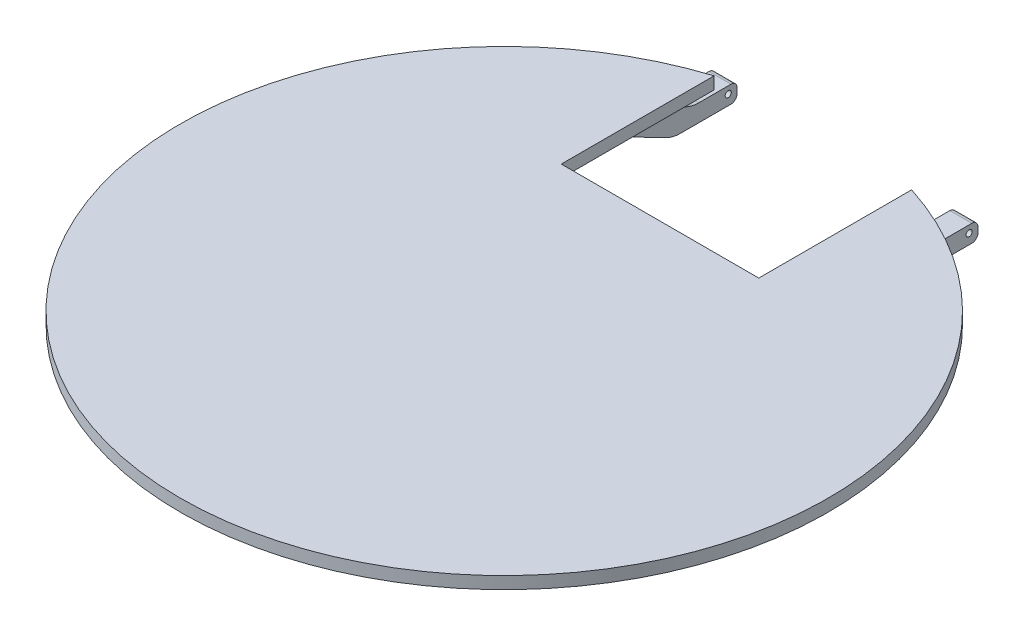
SolidWorks part; units mm, degrees
ref_plane "Piano frontale" through (0, 0, 0) normal (0, 0, 1) x (1, 0, 0)
ref_plane "Piano superiore" through (0, 0, 0) normal (0, 1, 0) x (1, 0, 0)
ref_plane "Piano destro" through (0, 0, 0) normal (1, 0, 0) x (0, 0, -1)
sketch "Schizzo1" plane through (0, 0, 0) normal (0, 1, 0) x (1, 0, 0)
  line L0 (0, -1000) -> (0, 49000) construction
  line L1 (0, 106) -> (32.3, 106)
  line L2 (32.3, 106) -> (32.3, 100.959)
  line L3 (0, 106) -> (-32.3, 106)
  line L4 (-32.3, 106) -> (-32.3, 100.959)
  line L5 (-32.3, 100.959) -> (-32.3, 50.959)
  line L6 (-32.3, 50.959) -> (32.3, 50.959)
  line L7 (32.3, 50.959) -> (32.3, 100.959)
  arc A0 (-32.3, 100.959) -> (32.3, 100.959) centre (0, 0) ccw
extrude "Estrusione-Estrusione1" add sketch "Schizzo1" along normal blind 4 contours L0 A0 L7 L6 | A0 L0 L6 L5 region at (-48.1372, 0, 8.4084) region at (48.1372, 0, 8.4084)
sketch "Schizzo2" plane through (0, 0, 0) normal (0, -1, 0) x (1, 0, 0)
  line L0 (32.3, -50.959) -> (35.8, -50.959) construction
  line L1 (35.8, -50.959) -> (35.8, -99.7715) construction
  line L2 (35.8, -99.7715) -> (35.8, -89.7715) construction
  line L4 (35.8, -89.7715) -> (43, -89.7715)
  line L5 (35.8, -89.7715) -> (35.8, -69.7715)
  line L6 (35.8, -69.7715) -> (43, -69.7715)
  line L7 (43, -89.7715) -> (43, -69.7715)
  arc A0 (32.3, -100.959) -> (-32.3, -100.959) centre (0, 0) ccw construction
ref_plane "Piano1" through (35.8, 0, 0) normal (-1, 0, 0) x (0, 0, 1)
sketch "Schizzo3" plane through (35.8, 0, 0) normal (-1, 0, 0) x (0, 0, 1)
  line L0 (-100.959, 0) -> (-100.959, 4)
  line L1 (-100.959, 0) -> (-100.959, 4)
  line L2 (-100.959, 4) -> (106, 4)
  line L3 (-100.959, 4) -> (106, 4)
  line L4 (106, 4) -> (106, 0)
  line L5 (106, 4) -> (106, 0)
  line L6 (106, 0) -> (-100.959, 0)
  line L7 (106, 0) -> (-100.959, 0)
  line L8 (-100.959, 0) -> (-90.959, 0) construction
  line L9 (-100.959, 0) -> (-100.959, -7) construction
  line L10 (-100.959, -7) -> (-109.069, -7) construction
  line L11 (-90.959, 0) -> (-70.959, 0)
  line L12 (-70.959, 0) -> (-88.8039, -9.1917)
  line L13 (-93.383, -10.3017) -> (-109.9686, -10.3017)
  line L14 (-111.9686, -8.3017) -> (-111.9686, -6.634)
  line L15 (-109.9686, -4.634) -> (-99.4675, -4.634)
  line L16 (-91.6376, -0.8542) -> (-90.959, 0)
  circle A0 centre (-109.069, -7) radius 1
  arc A1 (-99.4675, -4.634) -> (-91.6376, -0.8542) centre (-99.4675, 5.366) ccw
  arc A2 (-88.8039, -9.1917) -> (-93.383, -10.3017) centre (-93.383, -0.3017) cw
  arc A3 (-109.9686, -10.3017) -> (-111.9686, -8.3017) centre (-109.9686, -8.3017) cw
  arc A4 (-111.9686, -6.634) -> (-109.9686, -4.634) centre (-109.9686, -6.634) cw
  dimension "D1" = 10
  dimension "D2" = 2
extrude "Estrusione-Estrusione2" add sketch "Schizzo3" against normal blind 7.2 separate body contours A4 L14 A3 L13 A2 L12 L7 L16 A1 L15 A0 region at (35.8, -5.4356, -93.1275)
pattern_linear "Ripetizione a L1" count 2 spacing 78.8 along (-1, 0, 0) of bodies 102
sketch "Schizzo4" plane through (0, 0, 0) normal (0, -1, 0) x (1, 0, 0)
  line L0 (0, 106) -> (0, 74) construction
  line L1 (0, 201000) -> (0, -249000) construction
  line L2 (106, 0) -> (68, 0) construction
  line L3 (0, 74) -> (68, 74) construction
  line L4 (68, 74) -> (68, -41)
  line L5 (68, -41) -> (-97.7497, -41)
  line L6 (68, 74) -> (-75.8947, 74)
  line L7 (32.3, -100.959) -> (32.3, -50.959)
  line L8 (32.3, -100.959) -> (32.3, -50.959)
  line L9 (32.3, -50.959) -> (-32.3, -50.959)
  line L10 (32.3, -50.959) -> (-32.3, -50.959)
  line L11 (-32.3, -50.959) -> (-32.3, -100.959)
  line L12 (-32.3, -50.959) -> (-32.3, -100.959)
  arc A0 (32.3, -100.959) -> (-32.3, -100.959) centre (0, 0) ccw construction
  arc A1 (32.3, -100.959) -> (-32.3, -100.959) centre (0, 0) ccw
  arc A2 (32.3, -100.959) -> (-32.3, -100.959) centre (0, 0) ccw
  arc M7 (32.3, -100.959) -> (-32.3, -100.959) centre (0, 0) ccw
extrude "Taglio-Estrusione1" cut sketch "Schizzo4" against normal blind 0.0001 contours L4 L6 L5 M7 region at (-15.682, 0, 15.3425)
